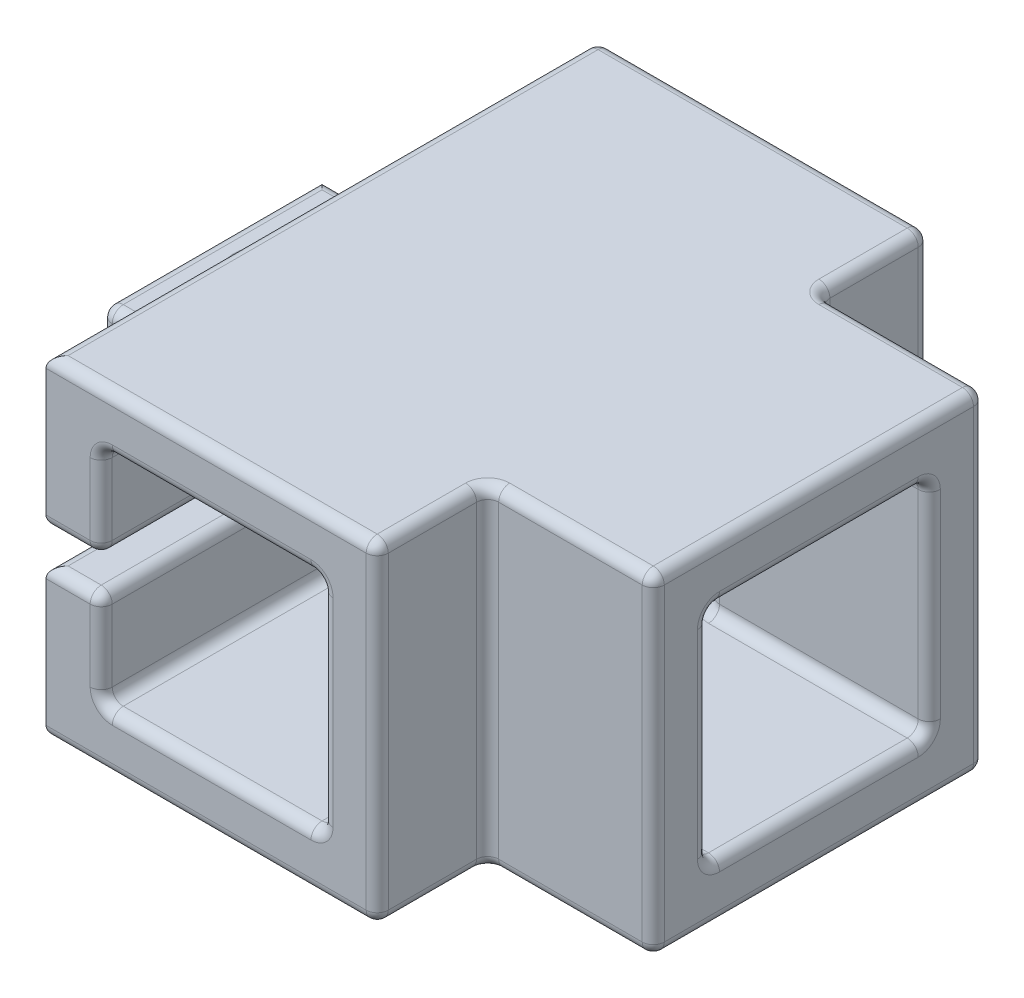
SolidWorks part; units mm, degrees
material "20% infill ABS"
ref_plane "Front Plane" through (0, 0, 0) normal (0, 0, 1) x (1, 0, 0)
ref_plane "Top Plane" through (0, 0, 0) normal (0, 1, 0) x (1, 0, 0)
ref_plane "Right Plane" through (0, 0, 0) normal (1, 0, 0) x (0, 0, -1)
sketch "Sketch1" plane through (0, 0, 0) normal (0, 0, 1) x (1, 0, 0)
  line L0 (-5.8424, 8.1021) -> (-5.8424, -11.8979)
  line L1 (-10.8424, 13.1021) -> (19.1576, 13.1021)
  line L2 (-10.8424, 13.1021) -> (-10.8424, -16.8979)
  line L3 (-10.8424, -16.8979) -> (19.1576, -16.8979)
  line L4 (19.1576, 13.1021) -> (19.1576, -16.8979)
  line L5 (-5.8424, -11.8979) -> (14.1576, -11.8979)
  line L6 (14.1576, 8.1021) -> (14.1576, -11.8979)
  line L7 (-5.8424, 8.1021) -> (14.1576, 8.1021)
  dimension "D1" = 30
  dimension "D2" = 30
  dimension "D3" = 5
extrude "Boss-Extrude1" add sketch "Sketch1" along normal blind 50
sketch "Sketch2" plane through (19.1576, 0, 0) normal (1, 0, 0) x (0, 0, -1)
  line L0 (-25, 13.1021) -> (-10, 13.1021)
  line L1 (-50, 13.1021) -> (0, 13.1021) construction
  line L2 (-10, 13.1021) -> (-10, -16.8979)
  line L3 (-50, -16.8979) -> (0, -16.8979) construction
  line L4 (-10, -16.8979) -> (-40, -16.8979)
  line L5 (-40, -16.8979) -> (-40, 13.1021)
  line L6 (-40, 13.1021) -> (-25, 13.1021)
  line L7 (-35, 8.1021) -> (-25, 8.1021)
  line L8 (-25, 8.1021) -> (-15, 8.1021)
  line L9 (-15, 8.1021) -> (-15, -11.8979)
  line L10 (-15, -11.8979) -> (-35, -11.8979)
  line L11 (-35, -11.8979) -> (-35, 8.1021)
  line L12 (-25, 13.1021) -> (-25, 8.1021) construction
  dimension "D1" = 5
  dimension "D2" = 20
  dimension "D3" = 5
  dimension "D4" = 5
  dimension "D5" = 5
extrude "Boss-Extrude2" add sketch "Sketch2" along normal blind 30 contours L6 L0 L2 L4 L5 | L7 L8 L9 L10 L11
sketch "Sketch3" plane through (19.1576, 0, 0) normal (1, 0, 0) x (0, 0, -1)
  line L0 (-35, 8.1021) -> (-15, 8.1021)
  line L1 (-15, 8.1021) -> (-15, -11.8979)
  line L2 (-15, -11.8979) -> (-35, -11.8979)
  line L3 (-35, -11.8979) -> (-35, 8.1021)
extrude "Cut-Extrude1" cut sketch "Sketch3" against normal blind 6
sketch "Sketch4" plane through (0, 0, 0) normal (0, 0, -1) x (-1, 0, 0)
  line L0 (5.8424, -11.8979) -> (5.8424, -1.8979)
  line L1 (5.8424, 8.1021) -> (5.8424, -11.8979) construction
  line L2 (5.8424, -1.8979) -> (5.8424, -0.3979)
  line L3 (5.8424, -0.3979) -> (10.8424, -0.3979)
  line L4 (10.8424, 13.1021) -> (10.8424, -16.8979) construction
  line L5 (10.8424, -0.3979) -> (20.8424, -0.3979)
  line L6 (20.8424, -0.3979) -> (20.8424, 4.6021)
  line L7 (20.8424, 4.6021) -> (10.8424, 4.6021)
  line L8 (10.8424, 4.6021) -> (10.8424, -0.3979)
  line L9 (10.8424, -0.3979) -> (10.8424, -3.3979)
  line L10 (10.8424, -3.3979) -> (20.8424, -3.3979)
  line L11 (20.8424, -3.3979) -> (20.8424, -8.3979)
  line L12 (20.8424, -8.3979) -> (10.8424, -8.3979)
  line L13 (10.8424, -8.3979) -> (10.8424, -3.3979)
  line M1 (10.8424, -16.8979) -> (10.8424, 13.1021)
extrude "Boss-Extrude3" add sketch "Sketch4" against normal blind 20 from offset 15 contours L6 L7 L5 M1 | L12 L11 L10 M1 region at (-15.8424, 2.1021, 0) region at (-15.8424, -5.8979, 0) offset against normal yes
sketch "Sketch5" plane through (0, 4.6021, 0) normal (0, 1, 0) x (1, 0, 0)
  line L0 (-20.8424, -15) -> (-10.8424, -35)
  circle A0 centre (-15.8424, -25) radius 2
extrude "Cut-Extrude2" cut sketch "Sketch5" against normal blind 30 contours L0 A0 | L0 A0 region at (-15.0832, 4.6021, 24.6204) region at (-16.6016, 4.6021, 25.3796)
sketch "Sketch6" plane through (0, 0, 50) normal (0, 0, 1) x (1, 0, 0)
  line L0 (-10.8424, -0.3979) -> (-5.8424, -0.3979)
  line L1 (-5.8424, 8.1021) -> (-5.8424, -11.8979) construction
  line L2 (-5.8424, -0.3979) -> (-5.8424, -3.3979)
  line L3 (-5.8424, -3.3979) -> (-10.8424, -3.3979)
  line L4 (-10.8424, 13.1021) -> (-10.8424, -16.8979) construction
  line L5 (-10.8424, -3.3979) -> (-10.8424, -0.3979)
extrude "Cut-Extrude3" cut sketch "Sketch6" against normal blind 140
sketch "Sketch7" plane through (49.1576, 0, 0) normal (1, 0, 0) x (0, 0, -1)
  line L1 (-10, 13.1021) -> (-40, 13.1021)
  line L2 (-10, 13.1021) -> (-10, -16.8979)
  line L3 (-10, -16.8979) -> (-40, -16.8979)
  line L4 (-40, 13.1021) -> (-40, -16.8979)
extrude "Cut-Extrude4" cut sketch "Sketch7" against normal blind 15
fillet "Fillet1" radius 1 54 edges at (-5.8424, -7.6479, 50) (-5.8424, -3.3979, 25) (24.1576, -11.8979, 35) (4.1576, -11.8979, 50) (-5.8424, -11.8979, 25) (24.1576, -11.8979, 15) (14.1576, -1.8979, 50) (14.1576, -11.8979, 42.5) (14.1576, -1.8979, 35) (14.1576, -11.8979, 7.5) (14.1576, -1.8979, 15) (24.1576, 8.1021, 15) (14.1576, 8.1021, 7.5) (4.1576, 8.1021, 50) (14.1576, 8.1021, 42.5) (24.1576, 8.1021, 35) (-5.8424, 3.8521, 50) (-5.8424, 8.1021, 25) (-5.8424, -0.3979, 25) (4.1576, 8.1021, 0) (14.1576, -1.8979, 0) (4.1576, -11.8979, 0) (-5.8424, -7.6479, 0) (-8.3424, -3.3979, 0) (-10.8424, -10.1479, 0) (-10.8424, 6.3521, 0) (-8.3424, -0.3979, 0) (-5.8424, 3.8521, 0) (19.1576, -1.8979, 0) (19.1576, -1.8979, 10) (34.1576, -1.8979, 35) (34.1576, -11.8979, 25) (34.1576, -1.8979, 15) (34.1576, 8.1021, 25) (34.1576, -1.8979, 10) (19.1576, -16.8979, 5) (4.1576, -16.8979, 0) (-10.8424, -16.8979, 25) (4.1576, -16.8979, 50) (34.1576, -16.8979, 25) (26.6576, -16.8979, 10) (26.6576, -16.8979, 40) (34.1576, -1.8979, 40) (19.1576, -1.8979, 50) (19.1576, -1.8979, 40) (19.1576, -16.8979, 45) (19.1576, 13.1021, 45) (4.1576, 13.1021, 50) (-10.8424, 13.1021, 25) (4.1576, 13.1021, 0) (19.1576, 13.1021, 5) (26.6576, 13.1021, 10) (34.1576, 13.1021, 25) (26.6576, 13.1021, 40)
fillet "Fillet2" radius 1 19 edges at (-10.8424, -5.8979, 35) (-10.5495, -3.6908, 0.2929) (-10.8424, -8.3979, 25) (-10.8424, -3.3979, 8) (-10.8424, 2.1021, 35) (-10.8424, 2.1021, 15) (-20.8424, -3.3979, 25) (-20.8424, -5.8979, 35) (-20.8424, -8.3979, 25) (-10.8424, -5.8979, 15) (-15.8424, -3.3979, 15) (-20.8424, -5.8979, 15) (-15.8424, -8.3979, 15) (-10.8424, 4.6021, 25) (-15.8424, 4.6021, 35) (-20.8424, 4.6021, 25) (-15.8424, 4.6021, 15) (-15.8424, 4.6021, 27) (-15.8424, -8.3979, 35)
fillet "Fillet3" radius 1 13 edges at (-20.5495, 4.3092, 34.7071) (-10.5495, -0.105, 0.2929) (-6.1353, -0.105, 49.7071) (-20.8424, 1.6021, 35) (-10.8424, -0.3979, 7.5) (-11.1353, -0.3979, 14.7071) (-16.3424, -0.3979, 15) (-20.8424, -0.3979, 25) (-16.3424, -0.3979, 35) (-11.1353, -0.3979, 35.2929) (-10.8424, -0.3979, 43) (-8.8424, -0.3979, 50) (-13.8424, -0.3979, 25)
fillet "Fillet4" radius 1 8 edges at (-6.1353, -3.6908, 49.7071) (-20.5495, -3.6908, 34.7071) (-15.8424, -3.3979, 23) (-8.8424, -3.3979, 50) (-10.8424, -3.3979, 43) (-11.1353, -3.3979, 35.2929) (-15.8424, -3.3979, 35) (-17.8424, -8.3979, 25)
